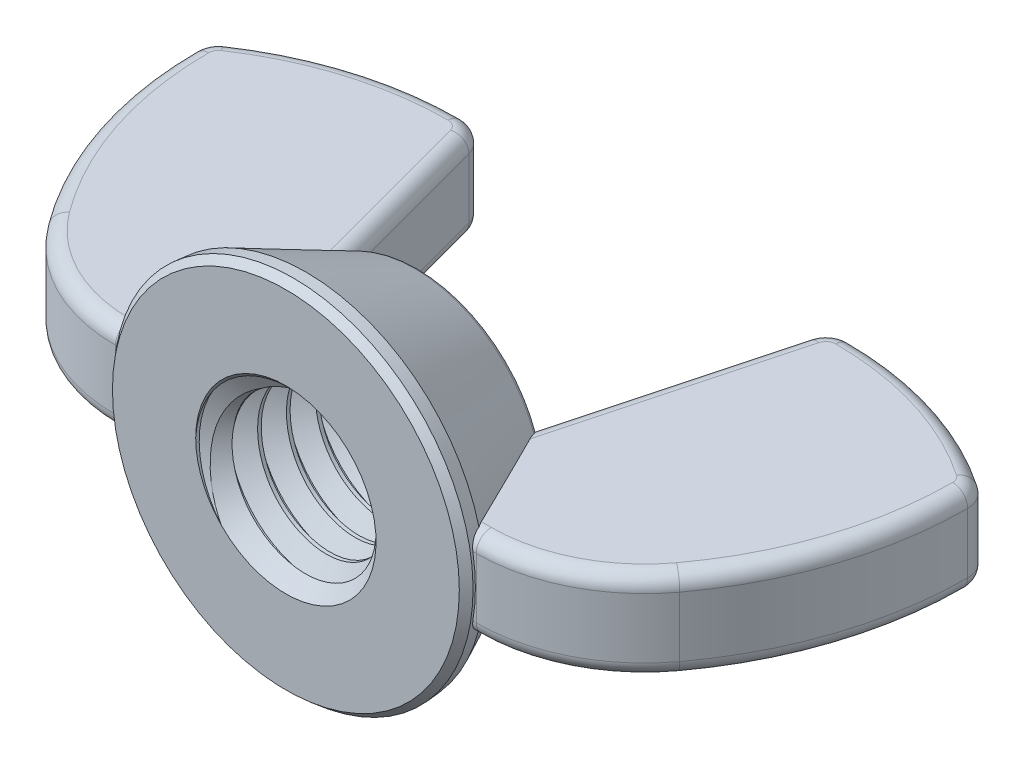
SolidWorks part; units mm, degrees
ref_plane "Front Plane" through (0, 0, 0) normal (0, 0, 1) x (1, 0, 0)
ref_plane "Top Plane" through (0, 0, 0) normal (0, 1, 0) x (1, 0, 0)
ref_plane "Right Plane" through (0, 0, 0) normal (1, 0, 0) x (0, 0, -1)
sketch "Sketch1" plane through (0, 0, 0) normal (0, 0, 1) x (1, 0, 0)
  circle A0 centre (0, 0) radius 2.5
  circle A1 centre (0, 0) radius 5
  dimension "thread dia" = 5
  dimension "C" = 10
sketch "Sketch2" plane through (0, 0, 0) normal (0, 1, 0) x (1, 0, 0)
  line L0 (0, 0) -> (0, 10.29) construction
  line L1 (-2.5, 0) -> (2.5, 0) construction
  line L2 (-10.73, 10.29) -> (10.73, 10.29) construction
  line L3 (10.73, 10.29) -> (10.73, 0) construction
  line L4 (-10.73, 10.29) -> (-10.73, 0) construction
  line L5 (-10.73, 0) -> (10.73, 0) construction
  line L6 (-3.4165, 3.7044) -> (3.4165, 3.7044) construction
  line L7 (0, 0) -> (0, 3.7044) construction
  line L8 (-4.3144, 0.5557) -> (5, 0.5557) construction
  line L9 (5, 0) -> (5, 3.7044) construction
  line L10 (3.0748, 3.7044) -> (4.8876, 10.4699)
  line L12 (3.4165, 3.7044) -> (3.4165, 0.2778) construction
  line L13 (-5, 0) -> (5, 0) construction
  line L14 (5, 0.5557) -> (3.4165, 3.7044) construction
  line L15 (4.8876, 10.4699) -> (11.019, 8.5954)
  line L16 (11.019, 8.5954) -> (6.9252, 0.2778)
  line L17 (5, 0.2778) -> (6.9252, 0.2778)
  line L19 (3.0748, 0.2778) -> (5, 0.2778)
  line L20 (-3.0748, 3.7044) -> (3.0748, 3.7044) construction
  line L21 (3.0748, 3.7044) -> (3.0748, 0.2778)
  line L22 (-5, 0) -> (5, 0) construction
  circle A3 centre (10.0356, 8.1699) radius 0.6944 construction
  circle A4 centre (5.3723, 9.5956) radius 0.6944 construction
  dimension "D6" = 1.3889
  dimension "D7" = 15
  dimension "D1" = 0.5557
  dimension "A" = 21.46
  dimension "B" = 10.29
  dimension "D2" = 3.7044
  dimension "D3" = 26.698
  dimension "D4" = 6.8329
  dimension "D5" = 0.2778
  dimension "D8" = 17
  dimension "D9" = 6.1496
  dimension "D10" = 10
sketch "Sketch13" plane through (0, 0, 0) normal (0, 1, 0) x (1, 0, 0)
  line L1 (3.0748, 3.7044) -> (3.0748, 0.2778) construction
  line L2 (3.0748, 3.7044) -> (4.8876, 10.4699) construction
  line L3 (-10.73, 10.29) -> (10.73, 10.29) construction
  line L4 (10.73, 10.29) -> (10.73, 0) construction
  line L5 (5, 0.2778) -> (6.9252, 0.2778) construction
  line L6 (3.0748, 0.2778) -> (5, 0.2778) construction
  line L7 (0, 0) -> (0, 3.7044) construction
  line L8 (-2.5, 0) -> (2.5, 0) construction
  line L9 (0, 0) -> (0, 10.29) construction
  line L10 (-3.4165, 3.7044) -> (3.4165, 3.7044) construction
  line L11 (3.0748, 0.2778) -> (5, 0.2778)
  line L12 (3.0748, 3.7044) -> (3.0748, 0.2778)
  line L13 (3.0748, 3.7044) -> (4.7015, 9.7753)
  circle A0 centre (10.0356, 8.1699) radius 0.6944 construction
  circle A1 centre (5.3723, 9.5956) radius 0.6944 construction
  arc A5 (10.73, 8.1699) -> (10.4239, 8.7456) centre (10.0356, 8.1699) ccw
  arc A6 (5.3723, 10.29) -> (4.7015, 9.7753) centre (5.3723, 9.5956) ccw
  arc A7 (8.7493, 2.1668) -> (10.73, 8.1699) centre (0.6427, 8.1699) ccw
  arc A8 (10.4239, 8.7456) -> (5.3723, 10.29) centre (5.3723, 1.2563) ccw
  arc A10 (5, 0.2778) -> (8.7493, 2.1668) centre (5, 4.9432) ccw
extrude "Extrude2" add sketch "Sketch13" along normal mid plane 2.5
sketch "Sketch3" plane through (0, 0, 0) normal (0, 0, 1) x (1, 0, 0)
  circle A0 centre (0, 0) radius 5 construction
  circle A1 centre (0, 0) radius 5
extrude "Extrude1" add sketch "Sketch3" against normal up to vertex (0.5557 mm away) draft 5 separate body up to point (5, 0, -0.5557)
sketch "Sketch15" plane through (0, 0, -0.5557) normal (0, 0, -1) x (-1, 0, 0)
  circle A1 centre (0, 0) radius 4.9514
  circle A2 centre (0, 0) radius 4.9514
  dimension "D1" = 0
extrude "Extrude3" add sketch "Sketch15" along normal up to vertex (3.1487 mm away) draft 25.21 up to point (0, 0, -3.7044)
fillet "Fillet3" radius 0.254 1 edges at (-3.469, 0, -3.7044)
sketch "Sketch12" plane through (0, 0, -3.7044) normal (0, 0, -1) x (-1, 0, 0)
  circle A1 centre (0, 0) radius 4.9514
  circle A2 centre (0, 0) radius 4.9514 construction
  dimension "D1" = 9.9028
sketch "Sketch4" plane through (0, 0, 0) normal (0, 0, 1) x (1, 0, 0)
  circle A0 centre (0, 0) radius 2.5 construction
  circle A1 centre (0, 0) radius 2.5
extrude "Cut-Extrude1" cut sketch "Sketch4" against normal through all
sketch "Sketch5" plane through (0, 0, 0) normal (0, 0, 1) x (1, 0, 0)
  circle A0 centre (0, 0) radius 2.5 construction
  circle A1 centre (0, 0) radius 2.5
curve "Helix/Spiral1" pitch 0.8 height 5.7044 turns 7.1305 parameters "pitch"=0.8
sketch "Sketch6" plane through (0, 0, 0) normal (0, 1, 0) x (1, 0, 0)
  line L0 (-2.5, -0.7) -> (-1.9804, -0.4)
  line L1 (-1.9804, -0.4) -> (-1.9804, -0.3)
  line L2 (-1.9804, -0.3) -> (-2.5, 0)
  line L3 (-2.5, -0.7) -> (-2.5, 0)
  line L4 (-2.5, -0.35) -> (-1.9804, -0.35) construction
  line L5 (-2.2402, -0.55) -> (-2.2402, -0.15) construction
  line L6 (-2.5, 0) -> (2.5, 0) construction
  dimension "D1" = 60
  dimension "D2" = 0.1
  dimension "D3" = 0.4
sweep "Sweep1" add profiles "Sketch6" path "Helix/Spiral1"
sketch "Sketch7" plane through (0, 0, 0) normal (0, 0, 1) x (1, 0, 0)
  circle A1 centre (0, 0) radius 5
  circle A2 centre (0, 0) radius 5
  dimension "D1" = 0
extrude "Cut-Extrude2" cut sketch "Sketch7" along normal through all
ref_plane "Plane1" through (0, 0, -3.7044) normal (0, 0, 1) x (1, 0, 0)
sketch "Sketch8" plane through (0, 0, -3.7044) normal (0, 0, 1) x (1, 0, 0)
  circle A0 centre (0, 0) radius 4.9514 construction
  circle A2 centre (0, 0) radius 4.9514
extrude "Cut-Extrude3" cut sketch "Sketch8" against normal through all
sketch "Sketch9" plane through (0, 0, 0) normal (0, 0, 1) x (1, 0, 0)
  circle A1 centre (0, 0) radius 2.5
  circle A2 centre (0, 0) radius 2.5
  dimension "D1" = 0
extrude "Cut-Extrude4" cut sketch "Sketch9" against normal through all draft 45
sketch "Sketch11" plane through (0, 0, -3.7044) normal (0, 0, 1) x (1, 0, 0)
  circle A0 centre (0, 0) radius 2.5 construction
  circle A1 centre (0, 0) radius 2.4492
  circle A2 centre (0, 0) radius 2.5 construction
  dimension "D1" = 0.0508
extrude "Cut-Extrude5" cut sketch "Sketch11" along normal through all draft 45
chamfer "Chamfer1" distance 0.2084 angle 45 1 edges at (5, 0, 0)
fillet "Fillet4" radius 0.4167 14 edges at (4.0374, 1.25, -0.2778) (7.0991, 1.25, -0.7767) (4.9495, 1.25, -10.1465) (8.0135, 1.25, -9.8953) (10.6487, 1.25, -8.4959) (4.0374, -1.25, -0.2778) (7.0991, -1.25, -0.7767) (4.9495, -1.25, -10.1465) (8.0135, -1.25, -9.8953) (10.6487, -1.25, -8.4959) (10.222, 1.25, -5.0092) (10.222, -1.25, -5.0092) (3.8882, 1.25, -6.7398) (3.8882, -1.25, -6.7398)
mirror "Mirror6" about plane through (0, 0, 0) normal (1, 0, 0) of bodies 108 113
combine bodies "Combine2" operation type add bodies to combine 116 108 107
sketch "Sketch16" plane through (0, 0, 0) normal (0, 1, 0) x (1, 0, 0)
  line L0 (-5, 0) -> (5, 0)
  dimension "D1" = 10
equation "\"D2@Sketch2\" = \"B@Sketch2\"*.36"
equation "\"D3@Helix/Spiral1\" = \"D2@Sketch2\"+2"
equation "\"D2@Sketch6\" = \"pitch@Helix/Spiral1\"*.125"
equation "\"D3@Sketch6\" = \"pitch@Helix/Spiral1\"*.5"
equation "\"D4@Sketch2\" = \"D1@Sketch12\"*.69"
equation "\"D1@Extrude2\" = \"C@Sketch1\"*.25"
equation "\"D1@Sketch2\" = \"D2@Sketch2\"*.150"
equation "\"D5@Sketch2\" = \"D1@Sketch2\"/2"
equation "\"D3@Extrude3\" = \"D3@Sketch2\""
equation "\"D1@Chamfer1\" = \"D5@Sketch2\"*.75"
equation "\"D9@Sketch2\" = \"D4@Sketch2\"*.9"
equation "\"D6@Sketch2\" = \"D1@Extrude2\"/1.8"
equation "\"D1@Fillet4\" = \"D1@Extrude2\"/6"
equation "\"D10@Sketch2\" = \"C@Sketch1\""
equation "\"D1@Sketch16\" = \"D10@Sketch2\""
